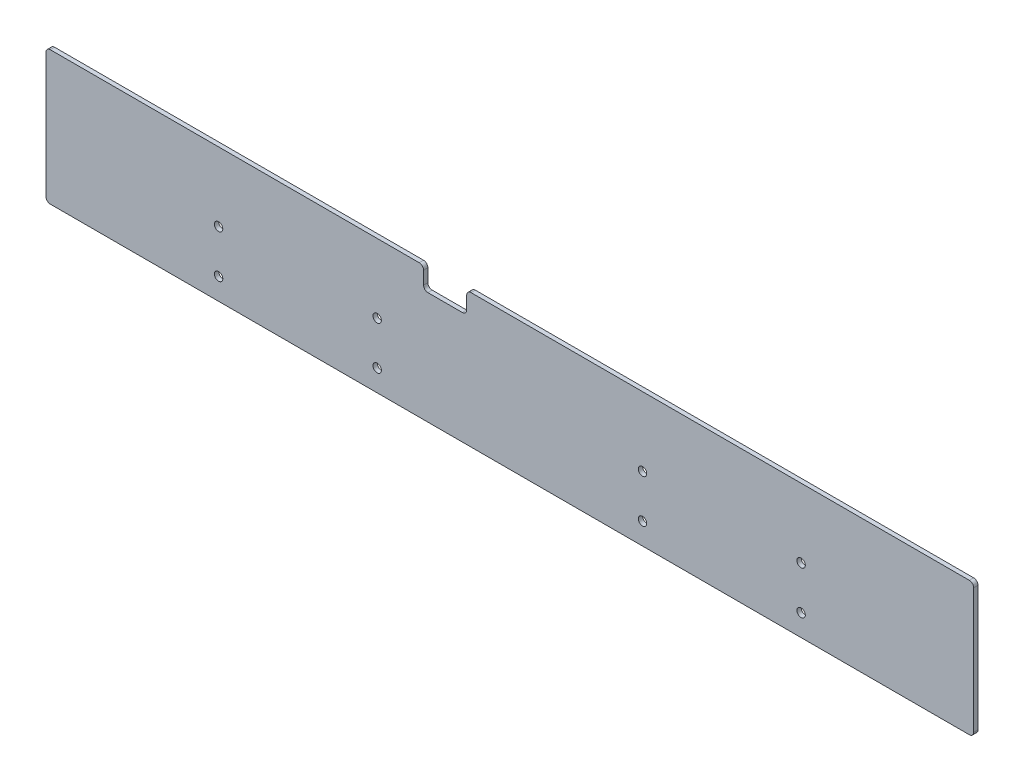
SolidWorks part; units mm, degrees
ref_plane "Front Plane" through (0, 0, 0) normal (0, 0, 1) x (1, 0, 0)
ref_plane "Top Plane" through (0, 0, 0) normal (0, 1, 0) x (1, 0, 0)
ref_plane "Right Plane" through (0, 0, 0) normal (1, 0, 0) x (0, 0, -1)
sketch "Sketch1" plane through (0, 0, 0) normal (0, 0, 1) x (1, 0, 0)
  line L0 (-161.9059, 17.7035) -> (73.0941, 17.7035)
  line L1 (-356.9059, 17.7035) -> (-181.9059, 17.7035)
  line L2 (-356.9059, 17.7035) -> (-356.9059, -44.2965)
  line L3 (-356.9059, -44.2965) -> (73.0941, -44.2965)
  line L4 (73.0941, 17.7035) -> (73.0941, -44.2965)
  line L6 (-181.9059, 17.7035) -> (-181.9059, 7.7035)
  line L7 (-181.9059, 7.7035) -> (-161.9059, 7.7035)
  line L8 (-161.9059, 17.7035) -> (-161.9059, 7.7035)
  circle A0 centre (-80.4059, -14.2965) radius 1.95
  circle A1 centre (-80.4059, -34.2965) radius 1.95
  circle A2 centre (-203.4059, -14.2965) radius 1.95
  circle A3 centre (-203.4059, -34.2965) radius 1.95
  dimension "D3" = 123
  dimension "D4" = 20
  dimension "D1" = 430
  dimension "D2" = 62
  dimension "D5" = 10
  dimension "D6" = 153.5
  dimension "D7" = 20
  dimension "D8" = 10
  dimension "D9" = 175
extrude "Boss-Extrude1" add sketch "Sketch1" along normal blind 2
fillet "Fillet1" radius 2 8 edges at (73.0941, -44.2965, 1) (-356.9059, -44.2965, 1) (-356.9059, 17.7035, 1) (-181.9059, 7.7035, 1) (-181.9059, 17.7035, 1) (-161.9059, 7.7035, 1) (-161.9059, 17.7035, 1) (73.0941, 17.7035, 1)
sketch "Sketch2" plane through (0, 0, 2) normal (0, 0, 1) x (1, 0, 0)
  line L0 (-354.9059, -44.2965) -> (71.0941, -44.2965) construction
  line L1 (-356.9059, 15.7035) -> (-356.9059, -42.2965) construction
  line L2 (73.0941, -42.2965) -> (73.0941, 15.7035) construction
  circle A0 centre (-276.9059, -14.2965) radius 1.95
  circle A1 centre (-276.9059, -34.2965) radius 1.95
  circle A2 centre (-6.9059, -14.2965) radius 1.95
  circle A3 centre (-6.9059, -34.2965) radius 1.95
  dimension "D1" = 20
  dimension "D2" = 10
  dimension "D3" = 80
  dimension "D4" = 80
  dimension "D5" = 20
  dimension "D6" = 10
extrude "Cut-Extrude1" cut sketch "Sketch2" against normal blind 10
